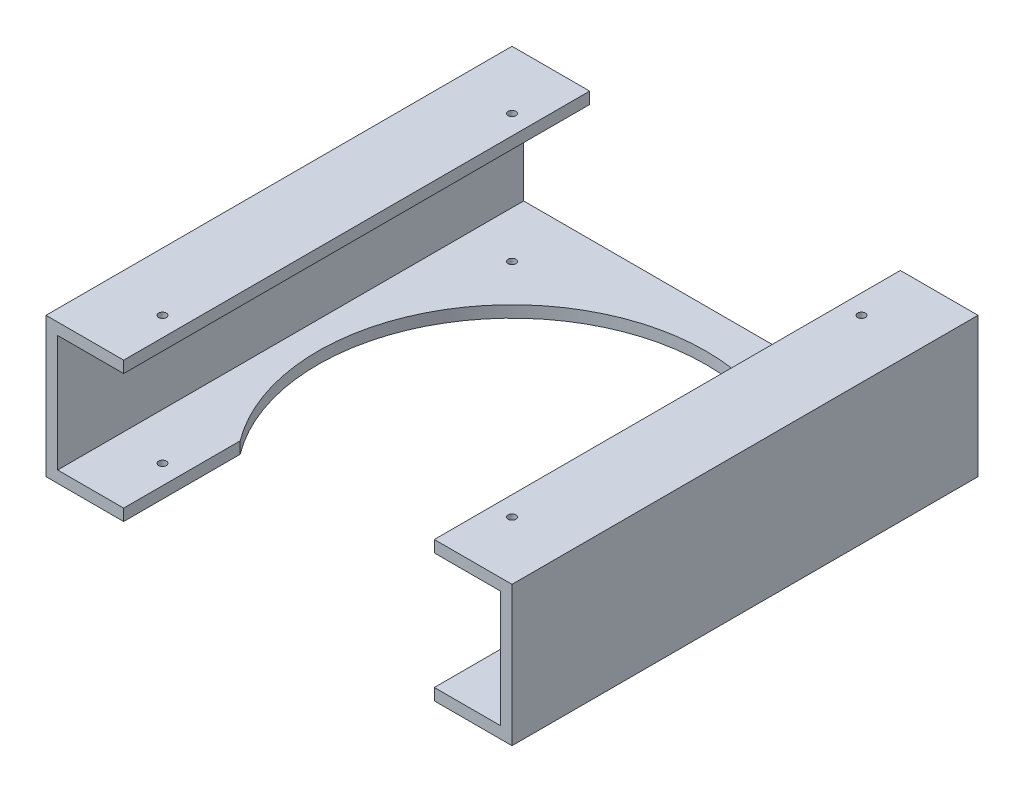
SolidWorks part; units mm, degrees
ref_plane "Front Plane" through (0, 0, 0) normal (0, 0, 1) x (1, 0, 0)
ref_plane "Top Plane" through (0, 0, 0) normal (0, 1, 0) x (1, 0, 0)
ref_plane "Right Plane" through (0, 0, 0) normal (1, 0, 0) x (0, 0, -1)
sketch "Sketch1" plane through (0, 0, 0) normal (0, 0, 1) x (1, 0, 0)
  line L1 (60, -18) -> (-60, -18)
  line L2 (60, -18) -> (60, 18)
  line L3 (60, 18) -> (-60, 18)
  line L4 (-60, -18) -> (-60, 18)
  line L5 (60, -18) -> (-60, 18) construction
  line L6 (60, 18) -> (-60, -18) construction
  point P0 (0, 0)
  dimension "D1" = 120
  dimension "D2" = 36
extrude "Boss-Extrude1" add sketch "Sketch1" along normal blind 60 and the other way blind 60
sketch "Sketch2" plane through (0, 0, 60) normal (0, 0, 1) x (1, 0, 0)
  line L0 (60, 18) -> (-60, 18) construction
  line L1 (57, -15) -> (-57, -15)
  line L2 (57, -15) -> (57, 15)
  line L3 (57, 15) -> (-57, 15)
  line L4 (-57, -15) -> (-57, 15)
  line L5 (57, -15) -> (-57, 15) construction
  line L6 (57, 15) -> (-57, -15) construction
  line L7 (60, -18) -> (60, 18) construction
  point P0 (0, 0)
  dimension "D1" = 3
  dimension "D2" = 3
extrude "Cut-Extrude1" cut sketch "Sketch2" against normal through all
sketch "Sketch3" plane through (0, 0, 60) normal (0, 0, 1) x (1, 0, 0)
  line L0 (57, 15) -> (-57, 15) construction
  line L1 (40, 3.8211) -> (-40, 3.8211)
  line L2 (40, 3.8211) -> (40, 26.1789)
  line L3 (40, 26.1789) -> (-40, 26.1789)
  line L4 (-40, 3.8211) -> (-40, 26.1789)
  line L5 (40, 3.8211) -> (-40, 26.1789) construction
  line L6 (40, 26.1789) -> (-40, 3.8211) construction
  line L7 (-60, 18) -> (-60, -18) construction
  point P0 (0, 15)
  dimension "D1" = 20
extrude "Cut-Extrude2" cut sketch "Sketch3" against normal through all
sketch "Sketch4" plane through (0, -15, 0) normal (0, 1, 0) x (1, 0, 0)
  circle A0 centre (0, 0) radius 50
  dimension "D1" = 100
extrude "Cut-Extrude3" cut sketch "Sketch4" against normal through all
sketch "Sketch5" plane through (0, -18, 0) normal (0, -1, 0) x (-1, 0, 0)
  line L1 (-55, 55) -> (55, 55) construction
  line L2 (-55, 55) -> (-55, -55) construction
  line L3 (-55, -55) -> (55, -55) construction
  line L4 (55, 55) -> (55, -55) construction
  line L5 (-55, 55) -> (55, -55) construction
  line L6 (-55, -55) -> (55, 55) construction
  point P0 (0, 0)
  dimension "D1" = 110
  dimension "D2" = 110
sketch "Sketch6" plane through (0, -18, 0) normal (0, -1, 0) x (-1, 0, 0)
  line L0 (-55, 55) -> (55, -55) construction
  line L1 (-45, 45) -> (45, 45) construction
  line L2 (-45, 45) -> (-45, -45) construction
  line L3 (-45, -45) -> (45, -45) construction
  line L4 (45, 45) -> (45, -45) construction
  line L5 (-45, 45) -> (45, -45) construction
  line L6 (-45, -45) -> (45, 45) construction
  point P0 (0, 0)
  dimension "D1" = 90
sketch "Sketch7" plane through (0, -18, 0) normal (0, -1, 0) x (-1, 0, 0)
  circle A0 centre (45, -45) radius 1
  circle A1 centre (-45, -45) radius 1
  circle A2 centre (-45, 45) radius 1
  circle A3 centre (45, 45) radius 1
  dimension "D1" = 2
extrude "Cut-Extrude4" cut sketch "Sketch7" against normal through all
sketch "Sketch8" plane through (0, -18, 0) normal (0, -1, 0) x (1, 0, 0)
  line L1 (-50, 0) -> (50, 0)
  line L2 (-50, 0) -> (-50, 80)
  line L3 (-50, 80) -> (50, 80)
  line L4 (50, 0) -> (50, 80)
  circle A0 centre (0, 0) radius 50 construction
  dimension "D1" = 80
  dimension "D2" = 100
extrude "Cut-Extrude5" [suppressed] cut sketch "Sketch8" against normal up to next
sketch "Sketch9" plane through (0, -18, 0) normal (0, -1, 0) x (1, 0, 0)
  line L0 (-60, 60) -> (60, 60) construction
  line L1 (40, 90) -> (-40, 90)
  line L2 (40, 90) -> (40, 30)
  line L3 (40, 30) -> (-40, 30)
  line L4 (-40, 90) -> (-40, 30)
  line L5 (40, 90) -> (-40, 30) construction
  line L6 (40, 30) -> (-40, 90) construction
  line L7 (-40, -60) -> (-40, 60) construction
  circle A0 centre (0, 0) radius 50 construction
  point P0 (0, 60)
extrude "Cut-Extrude6" cut sketch "Sketch9" against normal up to next
